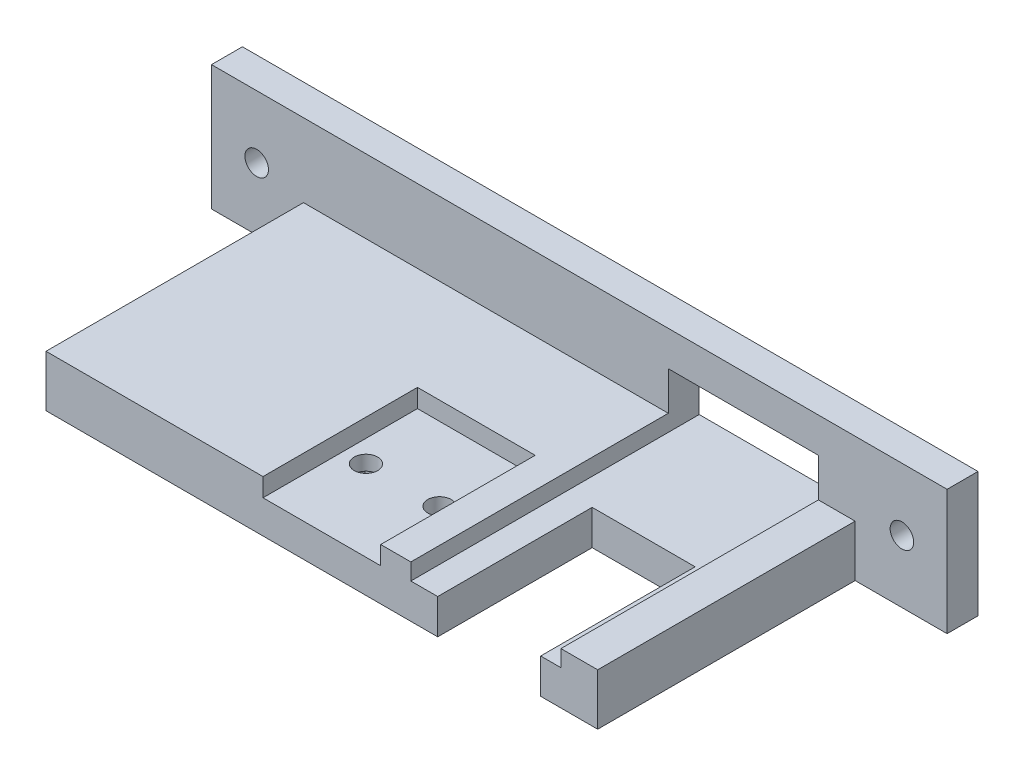
SolidWorks part; units mm, degrees
ref_plane "Front Plane" through (0, 0, 0) normal (0, 0, 1) x (1, 0, 0)
ref_plane "Top Plane" through (0, 0, 0) normal (0, 1, 0) x (1, 0, 0)
ref_plane "Right Plane" through (0, 0, 0) normal (1, 0, 0) x (0, 0, -1)
sketch "Sketch1" plane through (0, 0, 0) normal (0, 1, 0) x (1, 0, 0)
  line L0 (-37.5, -10.5) -> (37.5, -10.5)
  line L1 (-50, 10.5) -> (50, 10.5)
  line L2 (-50, 10.5) -> (-50, -10.5)
  line L3 (-50, -10.5) -> (50, -10.5)
  line L4 (50, 10.5) -> (50, -10.5)
  line L5 (-50, 10.5) -> (50, -10.5) construction
  line L6 (-50, -10.5) -> (50, 10.5) construction
  line L8 (-37.5, -10.5) -> (37.5, -10.5)
  line L9 (-37.5, -10.5) -> (-37.5, 6.2981)
  line L10 (-37.5, 6.2981) -> (37.5, 6.2981)
  line L11 (37.5, -10.5) -> (37.5, 6.2981)
  line L12 (-50, 10.5) -> (50, 10.5)
  line L13 (-50, 10.5) -> (-50, 6.2981)
  line L14 (-50, 6.2981) -> (50, 6.2981)
  line L15 (50, 10.5) -> (50, 6.2981)
  line L16 (37.5, 6.2981) -> (-37.5, 6.2981)
  line L17 (37.5, 6.2981) -> (37.5, -28.7019)
  line L18 (37.5, -28.7019) -> (-37.5, -28.7019)
  line L19 (-37.5, 6.2981) -> (-37.5, -28.7019)
  point P0 (0, 0)
  point P9 (0, -10.5)
  dimension "D1" = 100
  dimension "D2" = 21
  dimension "D3" = 75
  dimension "D4" = 16.7981
  dimension "D5" = 35
extrude "body" add sketch "Sketch1" along normal blind 7 contours L2 L14 L10 L4 L1 | L0 L11 L10 L9 | L17 L16 L19 L18 region at (0, 0, 2.101) region at (0, 0, -8.399)
sketch "Sketch3" plane through (0, 7, 0) normal (0, 1, 0) x (1, 0, 0)
  line L0 (0, 10.5) -> (0, -28.7019) construction
  line L1 (-50, 10.5) -> (50, 10.5) construction
  line L2 (37.5, -28.7019) -> (-37.5, -28.7019) construction
  line L3 (0, -28.7019) -> (0, -7.7019) construction
  line L4 (8, -7.7019) -> (-8, -7.7019)
  line L6 (-8, -7.7019) -> (8, -7.7019)
  line L7 (-8, -7.7019) -> (-8, -28.7019)
  line L8 (-8, -28.7019) -> (8, -28.7019)
  line L9 (8, -7.7019) -> (8, -28.7019)
  point P10 (0, -7.7019)
  line M11 (-37.5, -28.7019) -> (37.5, -28.7019)
  dimension "D1" = 21
  dimension "D2" = 16
extrude "chip-divet" cut sketch "Sketch3" against normal blind 2.5 contours L9 L4 L7 M11 region at (0, 7, 18.2019)
sketch "Sketch4" plane through (0, 4.5, 0) normal (0, 1, 0) x (1, 0, 0)
  line L0 (0, -7.7019) -> (0, -17.7019) construction
  line L1 (8, -7.7019) -> (-8, -7.7019) construction
  line L2 (5, -17.7019) -> (-5, -17.7019) construction
  circle A0 centre (-5, -17.7019) radius 1.6
  circle A1 centre (5, -17.7019) radius 1.6
  point P8 (0, -17.7019)
  dimension "D3" = 3.2
  dimension "D4" = 3.2
  dimension "D1" = 10
  dimension "D2" = 10
extrude "chip-mounting-holes" cut sketch "Sketch4" against normal through all
sketch "Sketch5" plane through (0, 0, 0) normal (0, -1, 0) x (1, 0, 0)
  line L1 (5.7448, 14.5384) -> (8.1121, 16.7652)
  line L2 (8.1121, 16.7652) -> (7.3673, 19.9287)
  line L3 (7.3673, 19.9287) -> (4.2552, 20.8654)
  line L4 (4.2552, 20.8654) -> (1.8879, 18.6386)
  line L5 (1.8879, 18.6386) -> (2.6327, 15.4751)
  line L6 (2.6327, 15.4751) -> (5.7448, 14.5384)
  line L7 (-4.2552, 14.5384) -> (-1.8879, 16.7652)
  line L8 (-1.8879, 16.7652) -> (-2.6327, 19.9287)
  line L9 (-2.6327, 19.9287) -> (-5.7448, 20.8654)
  line L10 (-5.7448, 20.8654) -> (-8.1121, 18.6386)
  line L11 (-8.1121, 18.6386) -> (-7.3673, 15.4751)
  line L12 (-7.3673, 15.4751) -> (-4.2552, 14.5384)
  circle A0 centre (5, 17.7019) radius 2.8146 construction
  circle A1 centre (-5, 17.7019) radius 2.8146 construction
  dimension "D1" = 6.5
  dimension "D2" = 6.5
extrude "chip-captive-nuts" cut sketch "Sketch5" against normal blind 2.5
sketch "Sketch6" plane through (0, 7, 0) normal (0, 1, 0) x (1, 0, 0)
  line L1 (37.5, -28.7019) -> (8, -28.7019)
  line L2 (37.5, -28.7019) -> (37.5, -7.7019)
  line L3 (37.5, -7.7019) -> (8, -7.7019)
  line L4 (8, -28.7019) -> (8, -7.7019)
  line L9 (27.0249, -7.7019) -> (18.4751, -28.7019) construction
  line L10 (27.0249, -28.7019) -> (18.4751, -7.7019) construction
  line L11 (29.75, -28.7019) -> (15.75, -28.7019)
  line L12 (29.75, -28.7019) -> (29.75, -7.7019)
  line L13 (29.75, -7.7019) -> (15.75, -7.7019)
  line L14 (15.75, -28.7019) -> (15.75, -7.7019)
  line L15 (29.75, -28.7019) -> (15.75, -7.7019) construction
  line L16 (29.75, -7.7019) -> (15.75, -28.7019) construction
  circle A0 centre (22.75, -18.2019) radius 7
  dimension "D1" = 14
extrude "routing-hole" cut sketch "Sketch6" against normal through all contours A0 | L12 L11 L14 L13 body kept at (37.5, 0, -6.2981)
sketch "Sketch7" plane through (0, 7, 0) normal (0, 1, 0) x (1, 0, 0)
  line L1 (50, 6.2981) -> (-50, 6.2981)
  line L2 (50, 6.2981) -> (50, 10.5)
  line L3 (50, 10.5) -> (-50, 10.5)
  line L4 (-50, 6.2981) -> (-50, 10.5)
extrude "face-plate" add sketch "Sketch7" along normal blind 10
sketch "Sketch8" plane through (0, 0, -10.5) normal (0, 0, -1) x (-1, 0, 0)
  line L0 (0, 17) -> (0, 0) construction
  line L1 (-50, 17) -> (50, 17) construction
  line L2 (50, 0) -> (-50, 0) construction
  line L3 (-32.5, 17) -> (32.5, 17) construction
  line L4 (-32.5, 17) -> (-32.5, 12.25) construction
  line L6 (-32.5, 12.25) -> (-12.1, 12.25)
  line L7 (-32.5, 12.25) -> (-32.5, 4.75)
  line L8 (-32.5, 4.75) -> (-12.1, 4.75)
  line L9 (-12.1, 12.25) -> (-12.1, 4.75)
  point P9 (0, 17)
  dimension "D1" = 65
  dimension "D2" = 4.75
  dimension "D3" = 20.4
  dimension "D4" = 7.5
extrude "switch-hole" cut sketch "Sketch8" against normal through all
sketch "Sketch2" plane through (0, 0, -10.5) normal (0, 0, -1) x (-1, 0, 0)
  line L0 (-50, 8.5) -> (-43.86, 8.5)
  line L1 (-50, 17) -> (-50, 0) construction
  line L2 (50, 8.5) -> (43.86, 8.5)
  line L3 (50, 17) -> (50, 0) construction
  circle A0 centre (-43.86, 8.5) radius 1.6
  circle A1 centre (43.86, 8.5) radius 1.6
  dimension "D3" = 3.2
  dimension "D4" = 3.2
  dimension "D1" = 6.14
  dimension "D2" = 6.14
extrude "mounting-holes" cut sketch "Sketch2" against normal through all contours A0 | A1 region at (43.86, 6.9453, -10.5) region at (-42.3053, 8.5, -10.5)
